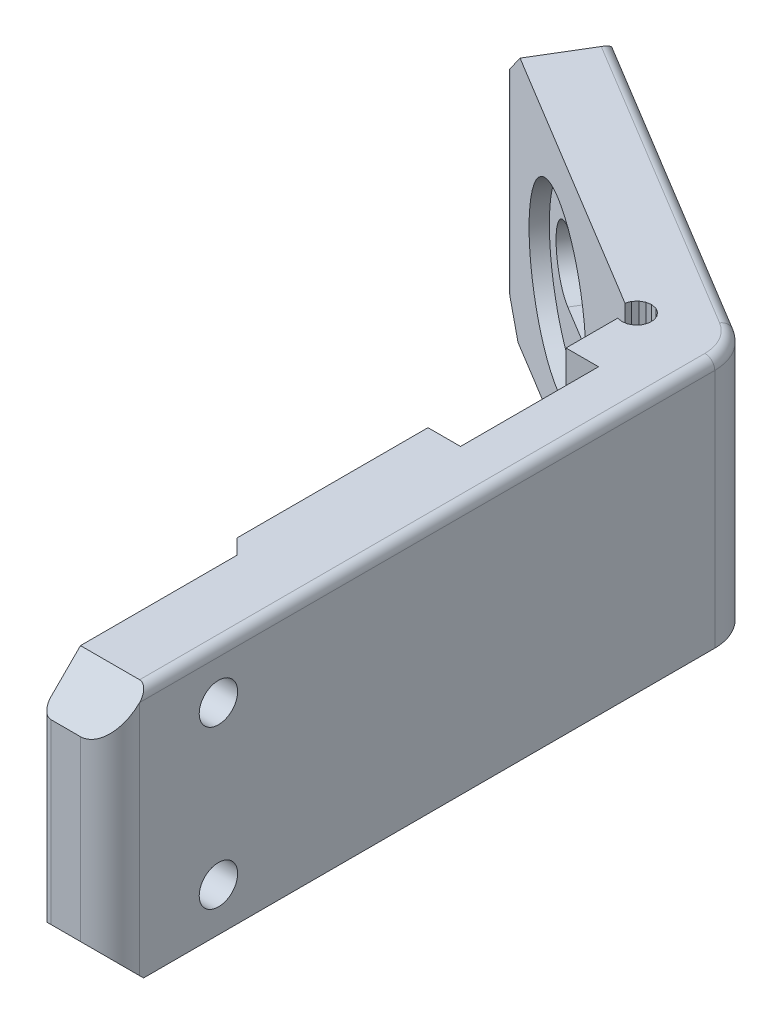
SolidWorks part; units mm, degrees
ref_plane "Front Plane" through (0, 0, 0) normal (0, 0, 1) x (1, 0, 0)
ref_plane "Top Plane" through (0, 0, 0) normal (0, 1, 0) x (1, 0, 0)
ref_plane "Right Plane" through (0, 0, 0) normal (1, 0, 0) x (0, 0, -1)
ref_plane "PY -20.700" through (0, -20.7, 0) normal (0, 1, 0) x (1, 0, 0)
sketch "leg and pad sketch" plane through (0, -20.7, 0) normal (0, 1, 0) x (1, 0, 0)
  line L0 (-0.5513, 30.3327) -> (-0.3673, 30.8194)
  line L1 (-0.3673, 30.8194) -> (-0.028, 31.2139)
  line L2 (-0.028, 31.2139) -> (0.4256, 31.4688)
  line L3 (0.4256, 31.4688) -> (0.939, 31.5534)
  line L4 (0.939, 31.5534) -> (1.4504, 31.4576)
  line L5 (1.4504, 31.4576) -> (1.8983, 31.1928)
  line L6 (1.8983, 31.1928) -> (2.2288, 30.7909)
  line L7 (2.2288, 30.7909) -> (2.4021, 30.3003)
  line L8 (2.4021, 30.3003) -> (2.3973, 29.78)
  line L9 (2.3973, 29.78) -> (2.2152, 29.2926)
  line L10 (2.2152, 29.2926) -> (1.8775, 28.8968)
  line L11 (1.8775, 28.8968) -> (1.4248, 28.6402)
  line L12 (1.4248, 28.6402) -> (0.9118, 28.5536)
  line L13 (0.9118, 28.5536) -> (0.4, 28.6475)
  line L14 (0.4, 28.6475) -> (0.4, -9.98)
  line L15 (0.4, -9.98) -> (1.92, -11.5)
  line L16 (1.92, -11.5) -> (1.92, -31.37)
  line L17 (1.92, -31.37) -> (8.92, -31.37)
  line L18 (8.92, -31.37) -> (8.92, 32.7926)
  line L19 (8.92, 32.7926) -> (-27.2048, 54.5947)
  line L20 (-27.2048, 54.5947) -> (-30.8218, 48.6015)
  line L21 (-30.8218, 48.6015) -> (-0.5513, 30.3327)
extrude "leg and pad" add sketch "leg and pad sketch" along normal mid plane 26
ref_plane "PX 1.350" through (1.35, 0, 0) normal (1, 0, 0) x (0, 0, -1)
sketch "screw head relief sketch" plane through (1.35, 0, 0) normal (1, 0, 0) x (0, 0, -1)
  line L0 (23.4, -12.7) -> (23.4, -6.7)
  line L1 (23.4, -6.7) -> (9.4, -6.7)
  line L2 (9.4, -6.7) -> (9.4, -12.7)
  line L3 (9.4, -12.7) -> (23.4, -12.7)
extrude "screw head relief" cut sketch "screw head relief sketch" against normal mid plane 4.7
sketch "insert flange relief sketch" plane through (0, -20.7, 0) normal (0, 1, 0) x (1, 0, 0)
  line L0 (-18.3249, 39.8914) -> (-17.0331, 42.0318)
  line L1 (-17.0331, 42.0318) -> (-9.7557, 37.6398)
  line L2 (-9.7557, 37.6398) -> (-11.0475, 35.4994)
  line L3 (-11.0475, 35.4994) -> (-18.3249, 39.8914)
revolve "insert flange relief" cut sketch "insert flange relief sketch" angle 360 about L0
sketch "M6 slot end 1 sketch" plane through (0, -20.7, 0) normal (0, 1, 0) x (1, 0, 0)
  line L0 (-20.8933, 41.4415) -> (-16.243, 49.147)
  line L1 (-16.243, 49.147) -> (-13.2464, 47.3385)
  line L2 (-13.2464, 47.3385) -> (-17.8968, 39.633)
  line L3 (-17.8968, 39.633) -> (-20.8933, 41.4415)
revolve "M6 slot end 1" cut sketch "M6 slot end 1 sketch" angle 360 about L0
sketch "M6 slot end 2 sketch" plane through (0, -20.7, 0) normal (0, 1, 0) x (1, 0, 0)
  line L0 (-15.7564, 38.3413) -> (-11.106, 46.0467)
  line L1 (-11.106, 46.0467) -> (-8.1094, 44.2382)
  line L2 (-8.1094, 44.2382) -> (-12.7598, 36.5328)
  line L3 (-12.7598, 36.5328) -> (-15.7564, 38.3413)
revolve "M6 slot end 2" cut sketch "M6 slot end 2 sketch" angle 360 about L0
sketch "M6 slot middle sketch" plane through (0, -20.7, 0) normal (0, 1, 0) x (1, 0, 0)
  line L0 (-15.7564, 38.3413) -> (-20.8933, 41.4415)
  line L1 (-20.8933, 41.4415) -> (-16.243, 49.147)
  line L2 (-16.243, 49.147) -> (-11.106, 46.0467)
  line L3 (-11.106, 46.0467) -> (-15.7564, 38.3413)
extrude "M6 slot middle" cut sketch "M6 slot middle sketch" against normal mid plane 7
ref_plane "PX 5.420" through (5.42, 0, 0) normal (1, 0, 0) x (0, 0, -1)
sketch "screw holes sketch" plane through (5.42, 0, 0) normal (1, 0, 0) x (0, 0, -1)
  circle A0 centre (-20.375, -28.7) radius 1.95
  circle A1 centre (-20.375, -12.7) radius 1.95
extrude "screw holes" cut sketch "screw holes sketch" against normal mid plane 9
chamfer "leg top corners" distance 4 angle 45 2 edges at (5.42, -7.7, 31.37) (5.42, -33.7, 31.37) tangent propagation no
chamfer "pad end corners" distance 4 angle 45 2 edges at (-29.0133, -7.7, -51.5981) (-29.0133, -33.7, -51.5981) tangent propagation no
fillet "outside of the bend" radius 5 1 edges at (8.92, -20.7, -32.7926) tangent propagation no
fillet "leg top outer edge" radius 3 1 edges at (8.92, -20.7, 31.37) tangent propagation no
fillet "pad end outer edge" radius 3 1 edges at (-27.2048, -20.7, -54.5947) tangent propagation no
fillet "leg top inner edge" radius 1 1 edges at (1.92, -20.7, 31.37) tangent propagation no
fillet "pad end inner edge" radius 1 1 edges at (-30.8218, -20.7, -48.6015) tangent propagation no
chamfer "bed face chamfer" distance 0.6 angle 45 6 edges at (-13.9742, -33.7, -38.4337) (-8.6383, -33.7, -43.3894) (1.92, -33.7, 19.435) (0.4, -33.7, -9.3337) (8.2742, -33.7, -32.4281) (8.92, -33.7, -1.3001)
fillet "top face edge" radius 1 3 edges at (-8.6383, -7.7, -43.3894) (8.2742, -7.7, -32.4281) (8.92, -7.7, -1.3001)
equation "\"diffL\" = 608.8mm"
equation "\"diffW\" = 329.4mm"
equation "\"diffT\" = 2.9mm"
equation "\"chanSlotW\" = 12.9mm"
equation "\"chanSlotDepth\" = 11.13mm"
equation "\"chanFloor\" = 1.57mm"
equation "\"chanLeg\" = 12.7mm"
equation "\"lightL\" = 605mm"
equation "\"lightW\" = 331mm"
equation "\"lightH\" = 92mm"
equation "\"lightSideFlat\" = 30mm"
equation "\"lightSlopeLen\" = 33.1mm"
equation "\"lightWingDepth\" = 47.9mm"
equation "\"lightWingFlat\" = 90.2mm"
equation "\"lightChanW\" = 99.6mm"
equation "\"lightChanStand\" = 44.1mm"
equation "\"insFlangeD\" = 12.3mm"
equation "\"insFromEnd\" = 20.7mm"
equation "\"insUpSlope\" = 20.8mm"
equation "\"gaugeH\" = 10mm"
equation "\"gaugeStepLen\" = 14mm"
equation "\"gaugeStepW0\" = 13.1mm"
equation "\"gaugeStepDW\" = 0.2mm"
equation "\"gaugeSteps\" = 5mm"
equation "\"gaugeHandleLen\" = 30mm"
equation "\"gaugeHandleW\" = 24mm"
equation "\"gaugeSlot0\" = 3mm"
equation "\"gaugeSlotD\" = 0.1mm"
equation "\"gaugeSlotDepth\" = 8mm"
equation "\"gap\" = 25.4mm"
equation "\"edgeL\" = 1mm"
equation "\"edgeW\" = 0.75mm"
equation "\"proud\" = 1.5mm"
equation "\"seatClr\" = 0.15mm"
equation "\"tongueClrZ\" = 0.1mm"
equation "\"tongueClrX\" = 0.25mm"
equation "\"tongueLen\" = 30mm"
equation "\"armSide\" = 45mm"
equation "\"armEnd\" = 20mm"
equation "\"cornerCham\" = 3mm"
equation "\"brkW\" = 26mm"
equation "\"brkT\" = 7mm"
equation "\"brkSeatClr\" = 0.2mm"
equation "\"brkScrewSpan\" = 16mm"
equation "\"pilotD\" = 2.7mm"
equation "\"pilotDepth\" = 10mm"
equation "\"screwClrD\" = 3.9mm"
equation "\"jogBelow\" = 4mm"
equation "\"padT\" = 7mm"
equation "\"padLen\" = 31mm"
equation "\"m6Clr\" = 7mm"
equation "\"m6Slot\" = 3mm"
equation "\"flangeRelD\" = 17mm"
equation "\"flangeRelDepth\" = 1.5mm"
equation "\"relLen\" = 7mm"
equation "\"relDepth\" = 4mm"
equation "\"relLand\" = 2mm"
equation "\"knockN\" = 100mm"
equation "\"petgcfE\" = 3000mm"
equation "\"mockExtent\" = 110mm"
equation "\"relZnear\" = 9.4mm"
equation "\"relZfar\" = 23.4mm"
equation "\"headD\" = 8mm"
equation "\"headH\" = 2.5mm"
equation "\"headFromEnd\" = 6.8mm"
equation "\"headBack\" = 16.4mm"
equation "\"sideClr\" = 0.4mm"
equation "\"cornerRelR\" = 1.5mm"
equation "\"cornerRelBack\" = 0.6mm"
equation "\"endHeadH\" = 2.8mm"
equation "\"footClr\" = 1.2mm"
equation "\"footEndClr\" = 3.5mm"
equation "\"footLift\" = 6mm"
equation "\"footBlockClr\" = 0.5mm"
equation "\"footBack\" = 50mm"
equation "\"footFwd\" = 10mm"
equation "\"footBraceEnd\" = 3mm"
equation "\"footLoadN\" = 25mm"
equation "\"spacerLen\" = 60mm"
equation "\"spacerShort\" = 0.5mm"
equation "\"spacerCham\" = 0.8mm"
equation "\"spacerPerSide\" = 3mm"
equation "\"spacerPerEnd\" = 1mm"
equation "\"toolR\" = 9mm"
equation "\"visR\" = 4mm"
equation "\"edgeR\" = 1mm"
equation "\"bendOutR\" = 5mm"
equation "\"insideR\" = 2.5mm"
equation "\"footCornerR\" = 10mm"
equation "\"footFrontR\" = 8mm"
equation "\"braceKinkR\" = 12mm"
equation "\"bedCham\" = 1mm"
equation "\"bedChamSmall\" = 0.6mm"
equation "\"soleTopR\" = 2mm"
